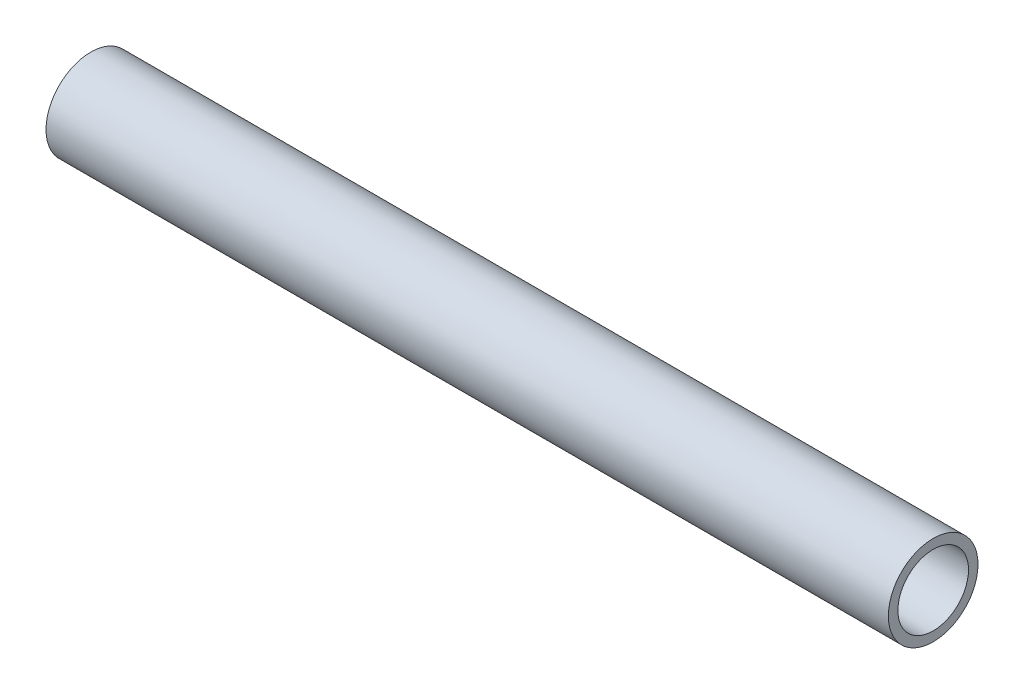
SolidWorks part; units mm, degrees
ref_plane "Front Plane" through (0, 0, 0) normal (0, 0, 1) x (1, 0, 0)
ref_plane "Top Plane" through (0, 0, 0) normal (0, 1, 0) x (1, 0, 0)
ref_plane "Right Plane" through (0, 0, 0) normal (1, 0, 0) x (0, 0, -1)
sketch "Sketch1" plane through (0, 0, 0) normal (1, 0, 0) x (0, 0, -1)
  circle A0 centre (0, 0) radius 8.509
  circle A1 centre (0, 0) radius 10.795
  dimension "D1" = 17.018
  dimension "D2" = 21.59
extrude "Boss-Extrude1" add sketch "Sketch1" along normal blind 203.2
chamfer "Chamfer1" distance 2.54 angle 45 1 edges at (0, 0, -8.509)
